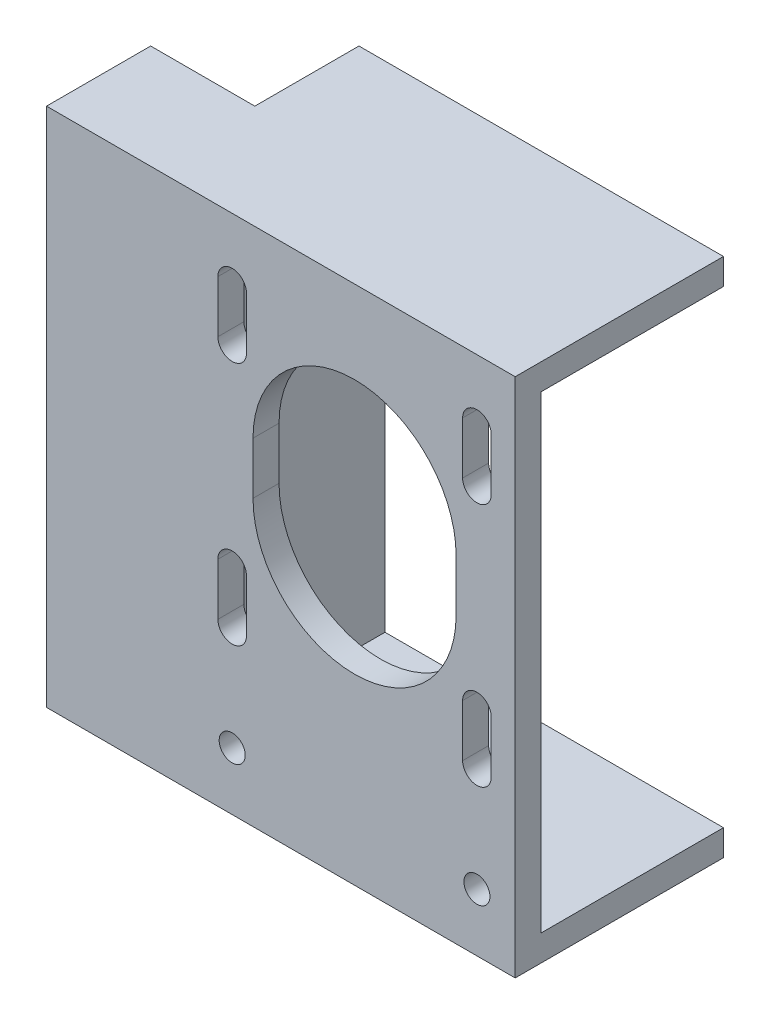
SolidWorks part; units mm, degrees
ref_plane "Front Plane" through (0, 0, 0) normal (0, 0, 1) x (1, 0, 0)
ref_plane "Top Plane" through (0, 0, 0) normal (0, 1, 0) x (1, 0, 0)
ref_plane "Right Plane" through (0, 0, 0) normal (1, 0, 0) x (0, 0, -1)
sketch "Sketch1" plane through (0, 0, 0) normal (0, 0, 1) x (1, 0, 0)
  line L1 (-47.788, 48.6636) -> (42.212, 48.6636)
  line L2 (-47.788, 48.6636) -> (-47.788, -51.3364)
  line L3 (-47.788, -51.3364) -> (42.212, -51.3364)
  line L4 (42.212, 48.6636) -> (42.212, -51.3364)
  dimension "D1" = 90
  dimension "D2" = 100
extrude "Boss-Extrude1" add sketch "Sketch1" along normal blind 20
sketch "Sketch2" plane through (0, 0, 0) normal (0, 0, -1) x (-1, 0, 0)
  line L0 (-42.212, 48.6636) -> (47.788, 48.6636) construction
  line L1 (27.788, 48.6636) -> (22.788, 48.6636)
  line L2 (27.788, 48.6636) -> (27.788, -51.3364)
  line L3 (27.788, -51.3364) -> (22.788, -51.3364)
  line L4 (22.788, 48.6636) -> (22.788, -51.3364)
  line L5 (47.788, -51.3364) -> (-42.212, -51.3364) construction
  line L6 (47.788, 48.6636) -> (47.788, -51.3364) construction
  dimension "D1" = 20
  dimension "D2" = 5
extrude "Boss-Extrude2" add sketch "Sketch2" along normal blind 20
sketch "Sketch3" plane through (0, 0, 0) normal (0, 0, -1) x (-1, 0, 0)
  line L0 (22.788, 48.6636) -> (22.788, -51.3364) construction
  line L1 (22.788, 43.6636) -> (-42.212, 43.6636)
  line L2 (22.788, 43.6636) -> (22.788, 48.6636)
  line L3 (22.788, 48.6636) -> (-42.212, 48.6636)
  line L4 (-42.212, 43.6636) -> (-42.212, 48.6636)
  line L5 (-42.212, -51.3364) -> (-42.212, 48.6636) construction
  line L6 (22.788, -51.3364) -> (-42.212, -51.3364)
  line L7 (22.788, -51.3364) -> (22.788, -46.3364)
  line L8 (22.788, -46.3364) -> (-42.212, -46.3364)
  line L9 (-42.212, -51.3364) -> (-42.212, -46.3364)
  dimension "D1" = 5
  dimension "D2" = 5
extrude "Boss-Extrude3" add sketch "Sketch3" along normal blind 20
sketch "Sketch5" plane through (0, 0, 20) normal (0, 0, 1) x (1, 0, 0)
  line L0 (-12.1349, -20.2339) -> (-12.1349, -10.2339) construction
  line L3 (-14.882, -20.2339) -> (-14.882, -10.2339)
  line L6 (-9.3878, -20.2339) -> (-9.3878, -10.2339)
  line L9 (11.3651, 3.2661) -> (11.3651, 13.2661) construction
  line L12 (-8.1349, 3.2661) -> (-8.1349, 13.2661)
  line L16 (30.8651, 3.2661) -> (30.8651, 13.2661)
  line L17 (34.8651, -20.2339) -> (34.8651, -10.2339) construction
  line L18 (32.118, -20.2339) -> (32.118, -10.2339)
  line L19 (37.6122, -20.2339) -> (37.6122, -10.2339)
  line L20 (34.8651, 26.7661) -> (34.8651, 36.7661) construction
  line L21 (32.118, 26.7661) -> (32.118, 36.7661)
  line L22 (37.6122, 26.7661) -> (37.6122, 36.7661)
  line L23 (-12.1349, 26.7661) -> (-12.1349, 36.7661) construction
  line L24 (-14.882, 26.7661) -> (-14.882, 36.7661)
  line L25 (-9.3878, 26.7661) -> (-9.3878, 36.7661)
  arc A12 (-14.882, -20.2339) -> (-9.3878, -20.2339) centre (-12.1349, -20.2339) ccw
  arc A13 (-9.3878, -10.2339) -> (-14.882, -10.2339) centre (-12.1349, -10.2339) ccw
  arc A14 (-8.1349, 3.2661) -> (30.8651, 3.2661) centre (11.3651, 3.2661) ccw
  arc A15 (30.8651, 13.2661) -> (-8.1349, 13.2661) centre (11.3651, 13.2661) ccw
  arc A16 (32.118, -20.2339) -> (37.6122, -20.2339) centre (34.8651, -20.2339) ccw
  arc A17 (37.6122, -10.2339) -> (32.118, -10.2339) centre (34.8651, -10.2339) ccw
  arc A18 (32.118, 26.7661) -> (37.6122, 26.7661) centre (34.8651, 26.7661) ccw
  arc A19 (37.6122, 36.7661) -> (32.118, 36.7661) centre (34.8651, 36.7661) ccw
  arc A20 (-14.882, 26.7661) -> (-9.3878, 26.7661) centre (-12.1349, 26.7661) ccw
  arc A21 (-9.3878, 36.7661) -> (-14.882, 36.7661) centre (-12.1349, 36.7661) ccw
  circle A22 centre (-12.1349, -40.2339) radius 2.5
  circle A23 centre (34.8651, -40.2339) radius 2.5
  point P2 (-12.1349, -15.2339)
  point P9 (11.3651, 8.2661)
  point P16 (34.8651, -15.2339)
  point P23 (34.8651, 31.7661)
  point P30 (-12.1349, 31.7661)
  dimension "D5" = 19.5
  dimension "D1" = 10
  dimension "D2" = 10
  dimension "D3" = 23.5
  dimension "D4" = 23.5
extrude "Cut-Extrude1" cut sketch "Sketch5" against normal blind 20
sketch "Sketch6" plane through (0, 0, 0) normal (0, 0, -1) x (-1, 0, 0)
  line L1 (-42.212, 43.6636) -> (22.788, 43.6636)
  line L2 (-42.212, 43.6636) -> (-42.212, -46.3364)
  line L3 (-42.212, -46.3364) -> (22.788, -46.3364)
  line L4 (22.788, 43.6636) -> (22.788, -46.3364)
extrude "Cut-Extrude2" cut sketch "Sketch6" against normal blind 15
